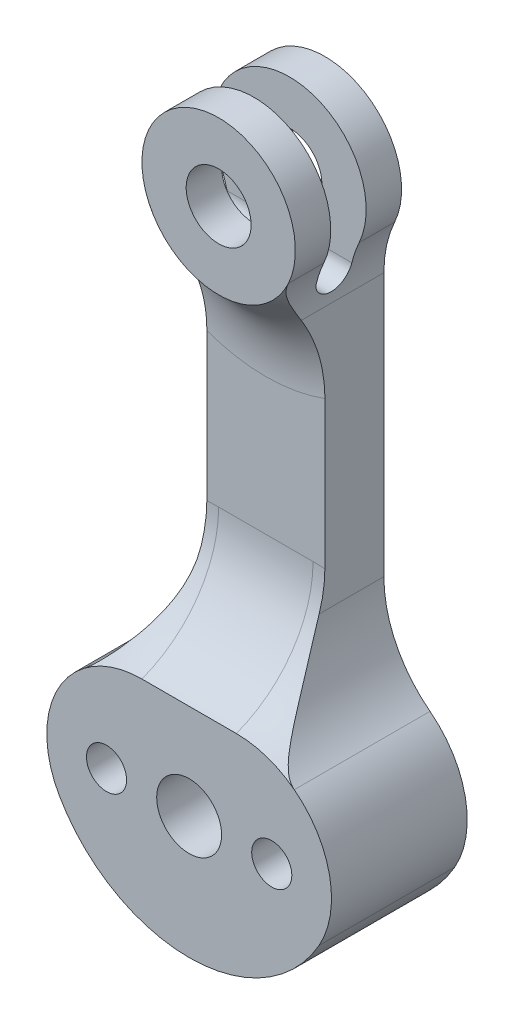
SolidWorks part; units mm, degrees
note: '?' marks a value the reader was unsure of.
other "Markup4"
sketch "Sketch18"
sketch "Sketch21" plane through (-12.0623, -47, 0) normal (-1, 0, 0) x (0, 0, -1)
material "Nylon 101"
ref_plane "Front Plane" through (0, 0, 0) normal (0, 0, 1) x (1, 0, 0)
ref_plane "Top Plane" through (0, 0, 0) normal (0, 1, 0) x (1, 0, 0)
ref_plane "Right Plane" through (0, 0, 0) normal (1, 0, 0) x (0, 0, -1)
sketch "Sketch1" plane through (0, 0, 0) normal (0, 0, 1) x (1, 0, 0)
  line L2 (-4, 0) -> (-4, -43.5)
  line L4 (4, 0) -> (4, -43.5)
  arc A3 (4, 0) -> (-4, 0) centre (0, 0) ccw
  arc A4 (-4, -43.5) -> (4, -43.5) centre (0, -43.5) ccw
  dimension "D1" = 43.5
  dimension "D2" = 4
extrude "Boss-Extrude1" add sketch "Sketch1" along normal blind 5
ref_plane "Plane1" through (0, 0, 5) normal (0, 0, 1) x (1, 0, 0)
sketch "Sketch2" plane through (0, 0, 5) normal (0, 0, 1) x (1, 0, 0)
  circle A0 centre (0, 0) radius 2.75
  circle A1 centre (0, -43.5) radius 2.75
  arc A2 (-4, -43.5) -> (4, -43.5) centre (0, -43.5) ccw construction
  dimension "D2" = 5.5
extrude "Cut-Extrude1" cut sketch "Sketch2" against normal through all
ref_plane "Plane2" through (0, 0, 5) normal (0, 0, 1) x (1, 0, 0)
sketch "Sketch3" plane through (0, 0, 5) normal (0, 0, 1) x (1, 0, 0)
  line L0 (4, -21.75) -> (-4, -21.75) construction
  line L1 (4, -43.5) -> (4, 0) construction
  line L2 (-4, 0) -> (-4, -43.5) construction
  circle A0 centre (0, -43.5) radius 4
  circle A1 centre (0, 0) radius 4
extrude "Boss-Extrude2" add sketch "Sketch3" along normal blind 6.5
ref_plane "Plane3" through (0, 0, 0) normal (0, 0, -1) x (-1, 0, 0)
sketch "Sketch4" plane through (0, 0, 0) normal (0, 0, -1) x (-1, 0, 0)
  line L0 (-4, -21.75) -> (4, -21.75) construction
  line L1 (-4, -43.5) -> (-4, 0) construction
  line L2 (4, 0) -> (4, -43.5) construction
  circle A0 centre (0, -43.5) radius 2.75
  circle A1 centre (0, -43.5) radius 2.75 construction
  circle A2 centre (0, 0) radius 2.75
extrude "Cut-Extrude2" cut sketch "Sketch4" against normal through all
ref_plane "Plane4" through (0, 0, 11.5) normal (0, 0, 1) x (1, 0, 0)
sketch "Sketch5" plane through (0, 0, 11.5) normal (0, 0, 1) x (1, 0, 0)
  circle A0 centre (0, 0) radius 4
extrude "Cut-Extrude3" cut sketch "Sketch5" against normal blind 2.5
ref_plane "Plane5" through (0, 0, 11.5) normal (0, 0, 1) x (1, 0, 0)
sketch "Sketch6" plane through (0, 0, 11.5) normal (0, 0, 1) x (1, 0, 0)
  line L0 (0, -43.5) -> (0, -47.5) construction
  line L1 (-4, -35.4377) -> (4, -35.4377)
  line L3 (-11, -47.5) -> (11, -47.5)
  line L4 (4, -43.5) -> (4, 0) construction
  line L5 (-4, 0) -> (-4, -43.5) construction
  circle A1 centre (0, -43.5) radius 2.75
  circle A2 centre (0, -43.5) radius 2.75 construction
  circle A3 centre (0, -43.5) radius 4 construction
  arc A4 (-4, -35.4377) -> (-11, -47.5) centre (-4, -43.5) ccw
  arc A5 (11, -47.5) -> (4, -35.4377) centre (4, -43.5) ccw
  arc A8 (-4, -43.5) -> (4, -43.5) centre (0, -43.5) ccw construction
  point P11 (0, -43.5)
  point P19 (0, -47.5)
  dimension "D1" = 11
  dimension "D2" = 11
extrude "Boss-Extrude3" add sketch "Sketch6" against normal up to surface (11.5 mm away) up to face at (2.75, 0, 0)
ref_plane "Plane7" through (0, 0, 0) normal (0, 0, -1) x (-1, 0, 0)
sketch "Sketch9" plane through (0, 0, 0) normal (0, 0, -1) x (-1, 0, 0)
  line L0 (0, -43.5) -> (50000, -43.5) construction
  line L1 (0, -43.5) -> (0, -26.1194) construction
  point P11 (7, -43.5)
  point P12 (-7, -43.5)
  dimension "D1" = 7
  dimension "D2" = 7
ref_plane "Plane9" through (0, 0, 0) normal (0, 0, -1) x (-1, 0, 0)
sketch "Sketch11" plane through (0, 0, 0) normal (0, 0, -1) x (-1, 0, 0)
  line L0 (-5, 0) -> (-5, -37.4377)
  line L1 (5, 0) -> (5, -37.4377)
  line L2 (5, -37.4377) -> (-5, -37.4377)
  arc A0 (5, 0) -> (-5, 0) centre (0, 0) ccw
  circle A3 centre (0, 0) radius 2.75
  circle A4 centre (0, 0) radius 2.75 construction
  dimension "D1" = 10
  dimension "D2" = 2
extrude "Boss-Extrude4" add sketch "Sketch11" against normal up to surface (5 mm away) up to face at (0, -18.7189, 5)
ref_plane "Plane10" through (0, 0, 9) normal (0, 0, 1) x (1, 0, 0)
sketch "Sketch12" plane through (0, 0, 9) normal (0, 0, 1) x (1, 0, 0)
  circle A0 centre (0, 0) radius 2.75
  circle A1 centre (0, 0) radius 6.5
  circle A2 centre (0, 0) radius 2.75 construction
  dimension "D1" = 13
extrude "Boss-Extrude5" add sketch "Sketch12" against normal up to surface (9 mm away) up to face at (0, -26.2981, 0)
ref_plane "Plane11" through (0, 0, 0) normal (0, 0, -1) x (-1, 0, 0)
fillet "Fillet2" radius 10 3 edges at (4.501, -35.4533, 5) (-4.501, -35.4533, 5) (0, -35.4377, 5)
fillet "Fillet3" radius 10 1 edges at (0, -6.5, 5)
hole_wizard "CBORE for M3 SBHCS1" positions "Sketch14" profile "Sketch15" counterbore size "M3" standard "ANSI Metric" end condition up to next
sketch "Sketch14" plane through (0, 0, 0) normal (0, 0, -1) x (-1, 0, 0)
  point P0 (7, -43.5)
  point P3 (-7, -43.5)
sketch "Sketch15" plane through (-7, -43.5, 0) normal (1, 0, 0) x (0, 1, 0)
  line L0 (0, 0) -> (0, 11.5)
  line L1 (0, 11.5) -> (1.7, 11.5)
  line L3 (1.7, 11.5) -> (1.7, 5)
  line L4 (1.7, 5) -> (3.125, 5)
  line L5 (3.125, 5) -> (3.125, 0)
  line L7 (3.125, 0) -> (0, 0)
  line L11 (0, -6.35) -> (0, 107.95) construction
  dimension "Thru Hole Dia." = 3.4
  dimension "Thru Hole Depth" = 11.5
  dimension "C'Bore Dia." = 6.25
  dimension "C'Bore Depth" = 5
fillet "Fillet4" radius 10 4 edges at (-5, -35.5, 5.75) (5, -35.5, 5.75) (-5, -4.1533, 4.5) (5, -4.1533, 4.5)
ref_plane "Plane12" through (0, 0, 4.5) normal (0, 0, -1) x (-1, 0, 0)
ref_axis "Axis1" through (0, 0, 0) along (0, 0, 1)?
sketch "Sketch19" plane through (0, 0, 0) normal (1, 0, 0) x (0, 0, -1)
  line L0 (0, -6.8739) -> (0, -29.1736) construction
  line L2 (-3, -4.5) -> (-3, 6.5)
  line L3 (-3, 6.5) -> (-6, 6.5)
  line L4 (-6, -4.5) -> (-6, 6.5)
  line L6 (0, -6.8739) -> (0, -29.1736)
  line L12 (-9, 6.5) -> (0, 6.5)
  arc A0 (-6, -4.5) -> (-3, -4.5) centre (-4.5, -4.5) ccw
  dimension "D1" = 3
  dimension "D2" = 11
extrude "Cut-Extrude4" cut sketch "Sketch19" against normal mid plane 20 contours L4 L3 L2 A0
sketch "Sketch20" plane through (0, 0, 0) normal (0, 0, -1) x (-1, 0, 0)
  circle A0 centre (0, 0) radius 4.75
  circle A1 centre (0, 0) radius 2.75 construction
  circle A2 centre (0, 0) radius 2.75
  dimension "D1" = 2
sketch "Sketch22" plane through (0, 0, 0) normal (0, 0, 1) x (1, 0, 0)
  line L0 (-11, -47.5) -> (11, -47.5)
  arc A0 (-11, -47.5) -> (11, -47.5) centre (0, -41.2143) ccw
  arc A1 (11, -47.5) -> (-11, -47.5) centre (0, -41.2143) ccw construction
extrude "Boss-Extrude6" add sketch "Sketch22" along normal up to surface (11.5 mm away) up to face at (-5.3, -43.5, 11.5)
